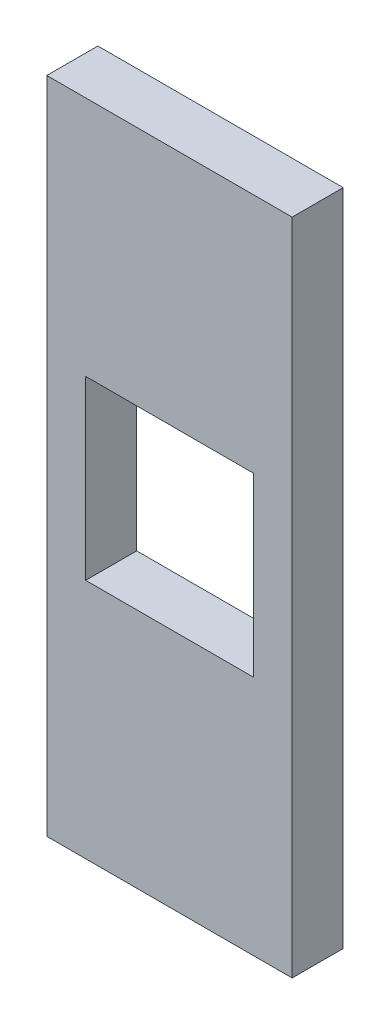
SolidWorks part; units mm, degrees
ref_plane "Front Plane" through (0, 0, 0) normal (0, 0, 1) x (1, 0, 0)
ref_plane "Top Plane" through (0, 0, 0) normal (0, 1, 0) x (1, 0, 0)
ref_plane "Right Plane" through (0, 0, 0) normal (1, 0, 0) x (0, 0, -1)
sketch "Sketch1" plane through (0, 0, 0) normal (0, 0, 1) x (1, 0, 0)
  line L0 (0, 67.15) -> (0, 44.75)
  line L1 (0, 67.15) -> (25, 67.15)
  line L2 (0, 44.75) -> (0, 39.55)
  line L3 (25, 0) -> (0, 0)
  line L4 (3.96, 42.575) -> (21.04, 42.575)
  line L5 (3.96, 24.575) -> (21.04, 24.575)
  line L6 (3.96, 42.575) -> (3.96, 24.575)
  line L7 (21.04, 42.575) -> (21.04, 24.575)
  line L8 (0, 44.75) -> (25, 44.75) construction
  line L9 (0, 39.55) -> (25, 39.55) construction
  line L10 (0, 39.55) -> (0, 27.6)
  line L11 (0, 27.6) -> (0, 22.4)
  line L12 (25, 44.75) -> (25, 39.55)
  line L13 (25, 67.15) -> (25, 44.75)
  line L14 (0, 22.4) -> (0, 0)
  line L15 (25, 39.55) -> (25, 27.6)
  line L16 (25, 27.6) -> (25, 22.4)
  line L17 (25, 22.4) -> (25, 0)
  line L18 (0, 27.6) -> (25, 27.6) construction
  line L19 (25, 22.4) -> (0, 22.4) construction
  line L20 (12.5, -0.0005) -> (12.5, 4.0956) construction
  point P18 (12.5, 24.575)
  point P20 (12.5, 42.575)
  point P21 (12.5, 67.15)
  dimension "D1" = 22.4
  dimension "D2" = 11.95
  dimension "D3" = 5.2
  dimension "D4" = 25
  dimension "D5" = 18
  dimension "D6" = 17.08
  dimension "D7" = 3.025
extrude "Boss-Extrude1" add sketch "Sketch1" along normal blind 5.2
